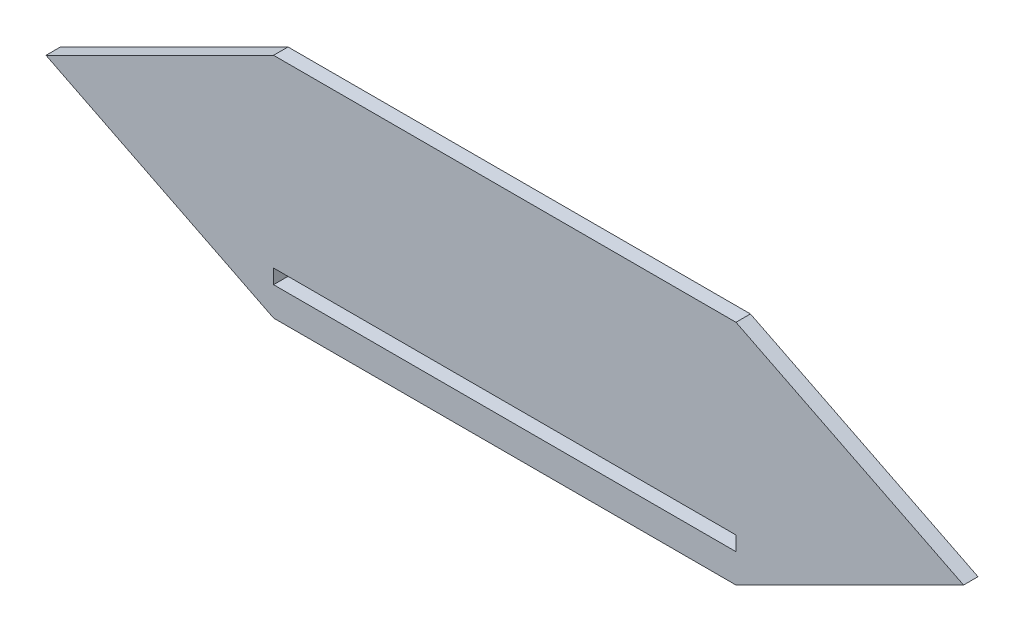
SolidWorks part; units mm, degrees
material "AISI 316 Annealed Stainless Steel Bar (SS)"
ref_plane "Front Plane" through (0, 0, 0) normal (0, 0, 1) x (1, 0, 0)
ref_plane "Top Plane" through (0, 0, 0) normal (0, 1, 0) x (1, 0, 0)
ref_plane "Right Plane" through (0, 0, 0) normal (1, 0, 0) x (0, 0, -1)
sketch "Sketch1" plane through (0, 0, 0) normal (0, 0, 1) x (1, 0, 0)
  line L0 (0, 50) -> (-100, 50) construction
  line L1 (0, 0) -> (203.2, 0)
  line L2 (0, 0) -> (0, 100)
  line L3 (0, 100) -> (203.2, 100)
  line L4 (203.2, 0) -> (203.2, 100)
  line L5 (101.6, 0) -> (101.6, 100) construction
  line L6 (0, 100) -> (-100, 50)
  line L7 (-100, 50) -> (0, 0)
  line L8 (303.2, 50) -> (203.2, 0)
  line L9 (203.2, 100) -> (303.2, 50)
  dimension "D3" = 100
  dimension "D1" = 203.2
  dimension "D2" = 100
extrude "Boss-Extrude1" add sketch "Sketch1" along normal blind 6.35 contours L2 | L4 | L1 L4 L3 L2 region at (101.6, 50, 0) region at (-33.3333, 50, 0) region at (236.5333, 50, 0)
sketch "Sketch2" plane through (0, 0, 0) normal (0, 0, -1) x (-1, 0, 0)
  line L0 (0, 0) -> (-203.2, 0) construction
  line L5 (-203.2, 6.7) -> (-177.8, 6.7)
  line L6 (-203.2, 6.7) -> (-203.2, 12.7)
  line L7 (-203.2, 12.7) -> (-177.8, 12.7)
  line L8 (-177.8, 6.7) -> (-177.8, 12.7)
  line L9 (6, 25.05) -> (6, 6.7)
  line L10 (-101.6, 0) -> (-101.6, 100) construction
  line L11 (0, 100) -> (-203.2, 100) construction
  line L20 (0, 6.7) -> (6, 6.7)
  line L21 (-203.2, 19.05) -> (-177.8, 19.05)
  line L22 (-203.2, 19.05) -> (-203.2, 25.05)
  line L23 (-203.2, 25.05) -> (-177.8, 25.05)
  line L24 (-177.8, 19.05) -> (-177.8, 25.05)
  line L25 (-203.2, 19.05) -> (-203.2, 12.7)
  line L26 (-203.2, 25.05) -> (-209.2, 25.05)
  line L31 (-203.2, 25.05) -> (-203.2, 6.7)
  line L36 (-203.2, 6.7) -> (-209.2, 6.7)
  line L37 (-209.2, 25.05) -> (-209.2, 6.7)
  line L38 (0, 25.05) -> (0, 6.7)
  line L39 (0, 25.05) -> (6, 25.05)
  line L40 (0, 19.05) -> (0, 12.7)
  line L41 (-25.4, 19.05) -> (-25.4, 25.05)
  line L50 (0, 25.05) -> (-25.4, 25.05)
  line L51 (0, 19.05) -> (0, 25.05)
  line L52 (0, 19.05) -> (-25.4, 19.05)
  line L53 (-25.4, 6.7) -> (-25.4, 12.7)
  line L54 (0, 12.7) -> (-25.4, 12.7)
  line L55 (0, 6.7) -> (0, 12.7)
  line L56 (0, 6.7) -> (-25.4, 6.7)
  dimension "D1" = 25.4
  dimension "D2" = 6.35
  dimension "D3" = 12.7
  dimension "D4" = 6
  dimension "D5" = 6
  dimension "D6" = 6
  dimension "D7" = 101.6
extrude "Boss-Extrude3" add sketch "Sketch2" along normal blind 25 contours L21 L24 L23 L22 | L26 L37 L36 L6 L25 L22 | L41 | L39 L38 L20 L9 | L56 L38 L54 L53 | L6 L5 L8 L7 region at (206.2, 15.875, 0) region at (190.5, 22.05, 0) region at (-3, 15.875, 0) region at (12.7, 22.05, 0) region at (12.7, 9.7, 0)
sketch "Sketch3" plane through (0, 0, 0) normal (0, 0, -1) x (-1, 0, 0)
  line L1 (-203.2, 12.7) -> (0, 12.7)
  line L2 (-203.2, 12.7) -> (-203.2, 19.05)
  line L3 (-203.2, 19.05) -> (0, 19.05)
  line L4 (0, 12.7) -> (0, 19.05)
extrude "Cut-Extrude1" cut sketch "Sketch3" against normal blind 10
